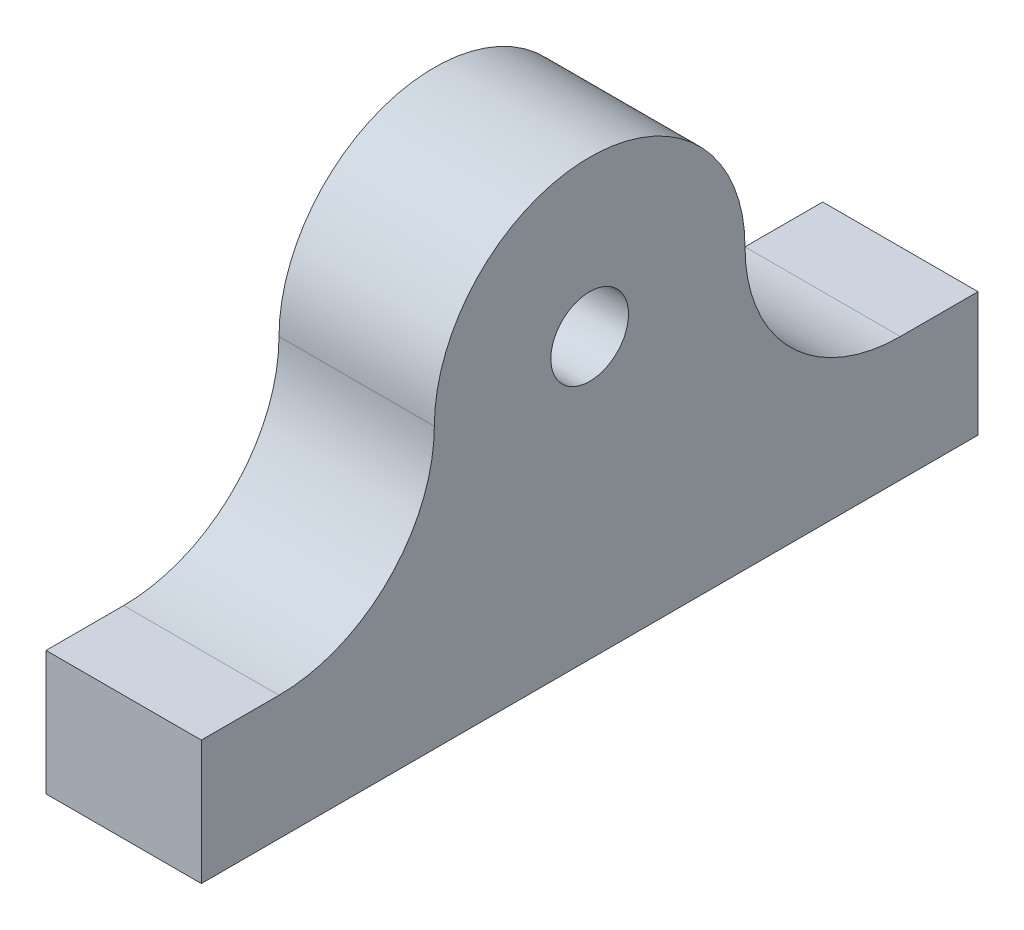
SolidWorks part; units mm, degrees
ref_plane "前基準面" through (0, 0, 0) normal (0, 0, 1) x (1, 0, 0)
ref_plane "上基準面" through (0, 0, 0) normal (0, 1, 0) x (1, 0, 0)
ref_plane "右基準面" through (0, 0, 0) normal (1, 0, 0) x (0, 0, -1)
ref_axis "基準軸1" through (0, -55, 0) along (0, 1, 0)
ref_axis "基準軸2" through (-88.99, 0, 0) along (1, 0, 0)
ref_axis "基準軸3" through (0, 0, 55) along (0, 0, -1)
sketch "草圖1" plane through (0, 0, 0) normal (1, 0, 0) x (0, 0, -1)
  line L0 (55, 0) -> (-55, 0) construction
  line L1 (-25, 0) -> (25, 0)
  line L2 (-25, 0) -> (-25, 8)
  line L3 (-25, 8) -> (-10, 8)
  line L4 (25, 0) -> (25, 8)
  line L5 (0, 55) -> (0, -55) construction
  line L6 (-10, 18) -> (-10, 8)
  line L7 (10, 18) -> (10, 8)
  line L8 (10, 8) -> (25, 8)
  arc A0 (10, 18) -> (-10, 18) centre (0, 18) ccw
  circle A1 centre (0, 18) radius 2.5
  dimension "D1" = 20
  dimension "D2" = 5
  dimension "D3" = 8
  dimension "D4" = 10
  dimension "D5" = 15
  dimension "D6" = 15
extrude "填料-伸長1" add sketch "草圖1" along normal blind 10
fillet "圓角1" radius 10 2 edges at (5, 8, -10) (5, 8, 10)
sketch "草圖2" plane through (0, 0, 0) normal (-1, 0, 0) x (0, 0, 1)
  circle A0 centre (0, 18) radius 2.5
  circle A1 centre (0, 18) radius 2.5 construction
  dimension "D1" = 5
ref_plane "平面1" through (-80, 0, 0) normal (1, 0, 0) x (0, 0, -1)
